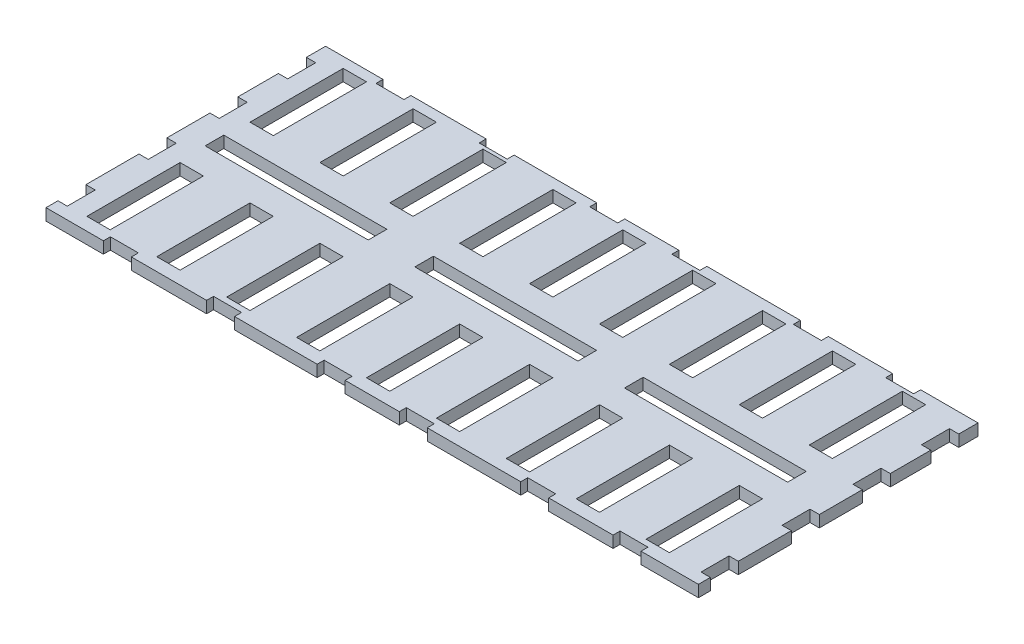
SolidWorks part; units mm, degrees
ref_plane "Front Plane" through (0, 0, 0) normal (0, 0, 1) x (1, 0, 0)
ref_plane "Top Plane" through (0, 0, 0) normal (0, 1, 0) x (1, 0, 0)
ref_plane "Right Plane" through (0, 0, 0) normal (1, 0, 0) x (0, 0, -1)
sketch "Sketch1" plane through (0, 0, 0) normal (0, 1, 0) x (1, 0, 0)
  line L0 (52, 115.5444) -> (52, 75.5444)
  line L1 (0, 0) -> (280, 0)
  line L2 (0, 0) -> (0, 120)
  line L3 (0, 120) -> (280, 120)
  line L4 (280, 0) -> (280, 120)
  line L5 (12, 115.5444) -> (22, 115.5444)
  line L6 (12, 115.5444) -> (12, 75.5444)
  line L7 (12, 75.5444) -> (22, 75.5444)
  line L8 (22, 115.5444) -> (22, 75.5444)
  line L9 (12, 115.5444) -> (22, 75.5444) construction
  line L10 (12, 75.5444) -> (22, 115.5444) construction
  line L11 (42, 115.5444) -> (42, 75.5444)
  line L12 (42, 75.5444) -> (52, 75.5444)
  line L13 (42, 115.5444) -> (52, 115.5444)
  line L14 (82, 115.5444) -> (82, 75.5444)
  line L15 (72, 115.5444) -> (72, 75.5444)
  line L16 (72, 75.5444) -> (82, 75.5444)
  line L17 (72, 115.5444) -> (82, 115.5444)
  line L18 (112, 115.5444) -> (112, 75.5444)
  line L19 (102, 115.5444) -> (102, 75.5444)
  line L20 (102, 75.5444) -> (112, 75.5444)
  line L21 (102, 115.5444) -> (112, 115.5444)
  line L22 (142, 115.5444) -> (142, 75.5444)
  line L23 (132, 115.5444) -> (132, 75.5444)
  line L24 (132, 75.5444) -> (142, 75.5444)
  line L25 (132, 115.5444) -> (142, 115.5444)
  line L26 (172, 115.5444) -> (172, 75.5444)
  line L27 (162, 115.5444) -> (162, 75.5444)
  line L28 (162, 75.5444) -> (172, 75.5444)
  line L29 (162, 115.5444) -> (172, 115.5444)
  line L30 (52, 45.5444) -> (52, 5.5444)
  line L31 (42, 45.5444) -> (42, 5.5444)
  line L32 (42, 5.5444) -> (52, 5.5444)
  line L33 (42, 45.5444) -> (52, 45.5444)
  line L34 (82, 45.5444) -> (82, 5.5444)
  line L35 (72, 45.5444) -> (72, 5.5444)
  line L36 (72, 5.5444) -> (82, 5.5444)
  line L37 (72, 45.5444) -> (82, 45.5444)
  line L38 (112, 45.5444) -> (112, 5.5444)
  line L39 (102, 45.5444) -> (102, 5.5444)
  line L40 (102, 5.5444) -> (112, 5.5444)
  line L41 (102, 45.5444) -> (112, 45.5444)
  line L42 (142, 45.5444) -> (142, 5.5444)
  line L43 (132, 45.5444) -> (132, 5.5444)
  line L44 (132, 5.5444) -> (142, 5.5444)
  line L45 (132, 45.5444) -> (142, 45.5444)
  line L46 (172, 45.5444) -> (172, 5.5444)
  line L47 (162, 45.5444) -> (162, 5.5444)
  line L48 (162, 5.5444) -> (172, 5.5444)
  line L49 (162, 45.5444) -> (172, 45.5444)
  line L50 (22, 45.5444) -> (22, 5.5444)
  line L51 (12, 45.5444) -> (12, 5.5444)
  line L52 (12, 5.5444) -> (22, 5.5444)
  line L53 (12, 45.5444) -> (22, 45.5444)
  line L54 (22, 115.5444) -> (52, 115.5444) construction
  line L55 (202, 115.5444) -> (202, 75.5444)
  line L56 (192, 75.5444) -> (202, 75.5444)
  line L57 (192, 115.5444) -> (192, 75.5444)
  line L58 (192, 115.5444) -> (202, 115.5444)
  line L59 (232, 115.5444) -> (232, 75.5444)
  line L60 (222, 75.5444) -> (232, 75.5444)
  line L61 (222, 115.5444) -> (222, 75.5444)
  line L62 (222, 115.5444) -> (232, 115.5444)
  line L63 (262, 115.5444) -> (262, 75.5444)
  line L64 (252, 75.5444) -> (262, 75.5444)
  line L65 (252, 115.5444) -> (252, 75.5444)
  line L66 (252, 115.5444) -> (262, 115.5444)
  line L67 (202, 45.5444) -> (202, 5.5444)
  line L68 (192, 5.5444) -> (202, 5.5444)
  line L69 (192, 45.5444) -> (192, 5.5444)
  line L70 (192, 45.5444) -> (202, 45.5444)
  line L71 (232, 45.5444) -> (232, 5.5444)
  line L72 (222, 5.5444) -> (232, 5.5444)
  line L73 (222, 45.5444) -> (222, 5.5444)
  line L74 (222, 45.5444) -> (232, 45.5444)
  line L75 (262, 45.5444) -> (262, 5.5444)
  line L76 (252, 5.5444) -> (262, 5.5444)
  line L77 (252, 45.5444) -> (252, 5.5444)
  line L78 (252, 45.5444) -> (262, 45.5444)
  line L79 (172, 45.5444) -> (172, 5.5444)
  line L80 (162, 5.5444) -> (172, 5.5444)
  line L81 (162, 45.5444) -> (162, 5.5444)
  line L82 (162, 45.5444) -> (172, 45.5444)
  line L83 (172, 115.5444) -> (202, 115.5444) construction
  point P5 (17, 95.5444)
  point P11 (12, 95.5444)
  dimension "D1" = 120
  dimension "D2" = 280
  dimension "D3" = 10
  dimension "D4" = 40
  dimension "D7" = 30
  dimension "D8" = 12
  dimension "D11" = 30
  dimension "D5" = 6
  dimension "D6" = 2
  dimension "D9" = 4
  dimension "D10" = 2
extrude "Boss-Extrude1" add sketch "Sketch1" along normal blind 5 contours L3 L4 L1 L2
extrude "Cut-Extrude1" cut sketch "Sketch1<3>" along normal blind 134 contours L62 L61 L60 L59 | L74 L73 L72 L71 | L70 L69 L68 L67 | L49 L47 L48 L46 | L29 L27 L28 L26 | L25 L23 L24 L22 | L21 L19 L20 L18 | L41 L39 L40 L38 | L37 L35 L36 L34 | L13 L11 L12 L0 | L33 L31 L32 L30 | L63 L64 L65 L66 | L75 L76 L77 L78 | L55 L56 L57 L58 | L43 L44 L42 L45 | L14 L16 L15 L17 | L51 L52 L50 L53 region at (47, 0, -95.5444) region at (107, 0, -95.5444) region at (137, 0, -95.5444) region at (167, 0, -95.5444) region at (47, 0, -25.5444) region at (77, 0, -25.5444) region at (107, 0, -25.5444) region at (167, 0, -25.5444) region at (227, 0, -95.5444) region at (197, 0, -25.5444) region at (227, 0, -25.5444)
sketch "Sketch1<3>" plane through (0, 0, 0) normal (0, 1, 0) x (1, 0, 0) same geometry as "Sketch1"
extrude "Cut-Extrude2" cut sketch "Sketch1<4>" along normal blind 229 contours L6 L7 L8 L5
sketch "Sketch1<4>" plane through (0, 0, 0) normal (0, 1, 0) x (1, 0, 0) same geometry as "Sketch1"
ref_plane "Plane1" through (0, 5, 0) normal (0, 1, 0) x (1, 0, 0)
sketch "Sketch3" plane through (0, 5, 0) normal (0, 1, 0) x (1, 0, 0)
  line L0 (0, 0) -> (0, 120) construction
  line L1 (0, 111.7407) -> (4, 111.7407)
  line L2 (0, 111.7407) -> (0, 99.7407)
  line L3 (0, 99.7407) -> (4, 99.7407)
  line L4 (4, 111.7407) -> (4, 99.7407)
  line L5 (140, 120) -> (140, 0) construction
  line L6 (0, 82.347) -> (4, 82.347)
  line L7 (0, 82.347) -> (0, 70.347)
  line L8 (0, 70.347) -> (4, 70.347)
  line L9 (4, 82.347) -> (4, 70.347)
  line L10 (0, 51.8956) -> (4, 51.8956)
  line L11 (0, 51.8956) -> (0, 39.8956)
  line L12 (0, 39.8956) -> (4, 39.8956)
  line L13 (4, 51.8956) -> (4, 39.8956)
  line L14 (0, 17.1285) -> (4, 17.1285)
  line L15 (0, 17.1285) -> (0, 5.1285)
  line L16 (0, 5.1285) -> (4, 5.1285)
  line L17 (4, 17.1285) -> (4, 5.1285)
  line L18 (0, 120) -> (280, 120) construction
  line L19 (0, 0) -> (280, 0) construction
  line L20 (280, 5.1285) -> (276, 5.1285)
  line L21 (276, 17.1285) -> (276, 5.1285)
  line L22 (280, 17.1285) -> (276, 17.1285)
  line L23 (280, 17.1285) -> (280, 5.1285)
  line L24 (280, 39.8956) -> (276, 39.8956)
  line L25 (276, 51.8956) -> (276, 39.8956)
  line L26 (280, 51.8956) -> (276, 51.8956)
  line L27 (280, 51.8956) -> (280, 39.8956)
  line L28 (280, 70.347) -> (276, 70.347)
  line L29 (276, 82.347) -> (276, 70.347)
  line L30 (280, 82.347) -> (276, 82.347)
  line L31 (280, 82.347) -> (280, 70.347)
  line L32 (280, 99.7407) -> (276, 99.7407)
  line L33 (276, 111.7407) -> (276, 99.7407)
  line L34 (280, 111.7407) -> (276, 111.7407)
  line L35 (280, 111.7407) -> (280, 99.7407)
  line L36 (163.627, 117) -> (151.627, 117)
  line L37 (24.6312, 120) -> (36.6312, 120)
  line L38 (24.6312, 120) -> (24.6312, 117)
  line L39 (24.6312, 117) -> (36.6312, 117)
  line L40 (36.6312, 120) -> (36.6312, 117)
  line L49 (116.373, 120) -> (128.373, 120)
  line L50 (116.373, 120) -> (116.373, 117)
  line L51 (116.373, 117) -> (128.373, 117)
  line L52 (128.373, 120) -> (128.373, 117)
  line L53 (151.627, 120) -> (151.627, 117)
  line L54 (163.627, 120) -> (151.627, 120)
  line L55 (163.627, 120) -> (163.627, 117)
  line L64 (255.3688, 117) -> (243.3688, 117)
  line L65 (243.3688, 120) -> (243.3688, 117)
  line L66 (255.3688, 120) -> (243.3688, 120)
  line L67 (255.3688, 120) -> (255.3688, 117)
  line L68 (0, 60) -> (280, 60) construction
  line L69 (280, 0) -> (280, 120) construction
  line L70 (255.3688, 0) -> (255.3688, 3)
  line L71 (255.3688, 0) -> (243.3688, 0)
  line L72 (243.3688, 0) -> (243.3688, 3)
  line L73 (255.3688, 3) -> (243.3688, 3)
  line L82 (163.627, 0) -> (163.627, 3)
  line L83 (163.627, 0) -> (151.627, 0)
  line L84 (151.627, 0) -> (151.627, 3)
  line L85 (163.627, 3) -> (151.627, 3)
  line L86 (116.373, 3) -> (128.373, 3)
  line L87 (128.373, 0) -> (128.373, 3)
  line L88 (116.373, 0) -> (128.373, 0)
  line L89 (116.373, 0) -> (116.373, 3)
  line L98 (24.6312, 3) -> (36.6312, 3)
  line L99 (36.6312, 0) -> (36.6312, 3)
  line L100 (24.6312, 0) -> (36.6312, 0)
  line L101 (24.6312, 0) -> (24.6312, 3)
  line L102 (203.7539, 117) -> (215.7539, 117)
  line L103 (68.9107, 0) -> (80.9107, 0)
  line L104 (68.9107, 0) -> (68.9107, 3)
  line L105 (68.9107, 3) -> (80.9107, 3)
  line L106 (80.9107, 0) -> (80.9107, 3)
  line L107 (203.7539, 0) -> (215.7539, 0)
  line L108 (203.7539, 0) -> (203.7539, 3)
  line L109 (203.7539, 3) -> (215.7539, 3)
  line L110 (215.7539, 0) -> (215.7539, 3)
  line L111 (215.7539, 120) -> (215.7539, 117)
  line L112 (203.7539, 120) -> (215.7539, 120)
  line L113 (203.7539, 120) -> (203.7539, 117)
  line L114 (68.9107, 117) -> (80.9107, 117)
  line L115 (80.9107, 120) -> (80.9107, 117)
  line L116 (68.9107, 120) -> (80.9107, 120)
  line L117 (68.9107, 120) -> (68.9107, 117)
  point P60 (0, 0)
  dimension "D1" = 4
  dimension "D2" = 12
  dimension "D3" = 4
  dimension "D4" = 12
  dimension "D5" = 4
  dimension "D6" = 12
  dimension "D7" = 4
  dimension "D8" = 12
  dimension "D9" = 12
  dimension "D10" = 3
  dimension "D15" = 12
  dimension "D16" = 3
  dimension "D17" = 12
  dimension "D18" = 3
  dimension "D19" = 12
sketch "Sketch4" plane through (0, 5, 0) normal (0, 1, 0) x (1, 0, 0)
  line L0 (101.1777, 65.1177) -> (171.1777, 65.1177)
  line L1 (11.1777, 65.1177) -> (81.1777, 65.1177)
  line L2 (11.1777, 65.1177) -> (11.1777, 57.1177)
  line L3 (11.1777, 57.1177) -> (81.1777, 57.1177)
  line L4 (81.1777, 65.1177) -> (81.1777, 57.1177)
  line L5 (11.1777, 65.1177) -> (81.1777, 57.1177) construction
  line L6 (11.1777, 57.1177) -> (81.1777, 65.1177) construction
  line L7 (101.1777, 57.1177) -> (171.1777, 57.1177)
  line L8 (101.1777, 65.1177) -> (101.1777, 57.1177)
  line L9 (171.1777, 65.1177) -> (171.1777, 57.1177)
  line L10 (191.1777, 65.1177) -> (261.1777, 65.1177)
  line L11 (191.1777, 57.1177) -> (261.1777, 57.1177)
  line L12 (191.1777, 65.1177) -> (191.1777, 57.1177)
  line L13 (261.1777, 65.1177) -> (261.1777, 57.1177)
  line L14 (11.1777, 65.1177) -> (101.1777, 65.1177) construction
  point P0 (46.1777, 61.1177)
  dimension "D1" = 70
  dimension "D2" = 8
  dimension "D4" = 90
  dimension "D3" = 3
extrude "Cut-Extrude4" cut sketch "Sketch4" against normal blind 229
extrude "Cut-Extrude5" cut sketch "Sketch3" against normal blind 10 contours L23 L22 L21 L20 | L100 L99 L98 L101 | L105 L106 L103 L104 | L86 L87 L88 L89 | L85 L84 L83 L82 | L107 L110 L109 L108 | L71 L72 L73 L70 | L27 L24 L25 L26 | L35 L32 L33 L34 | L29 L28 L31 L30 | L64 L65 L66 L67 | L112 L111 L102 L113 | L54 L53 L36 L55 | L49 L52 L51 L50 | L116 L115 L114 L117 | L37 L40 L39 L38 | L4 L3 L2 L1 | L9 L8 L7 L6 | L13 L12 L11 L10 | L15 L16 L17 L14 region at (278, 5, -11.1285)
